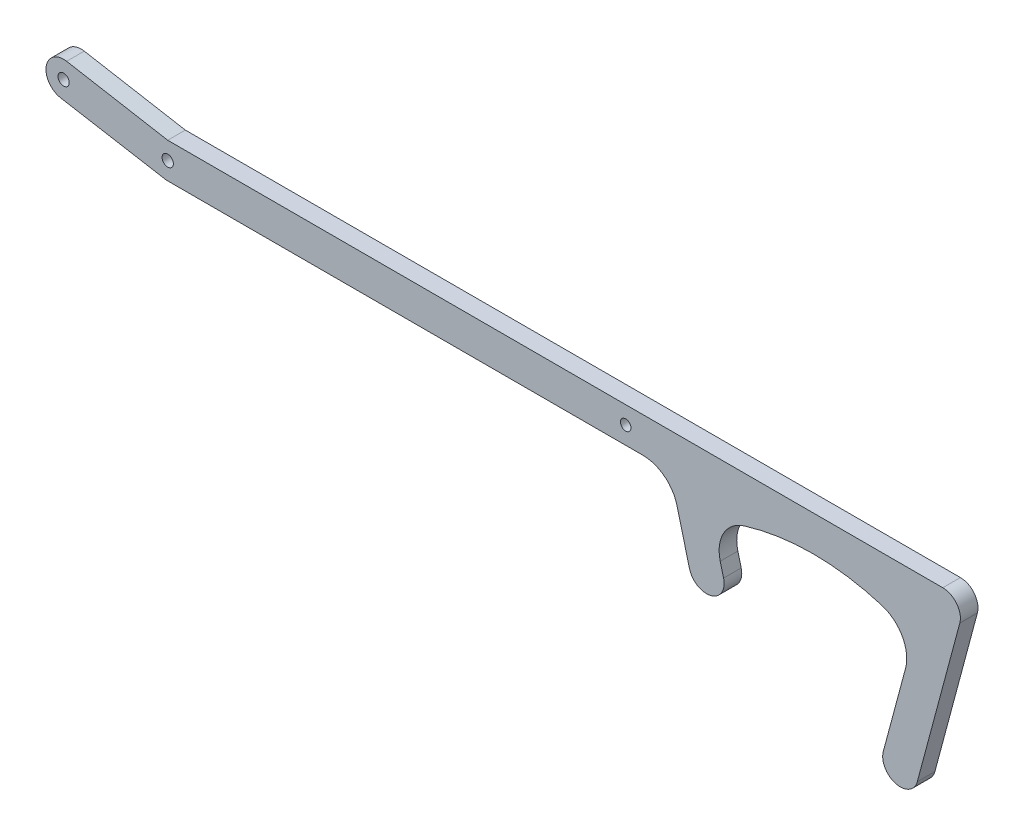
SolidWorks part; units mm, degrees
ref_plane "Front Plane" through (0, 0, 0) normal (0, 0, 1) x (1, 0, 0)
ref_plane "Top Plane" through (0, 0, 0) normal (0, 1, 0) x (1, 0, 0)
ref_plane "Right Plane" through (0, 0, 0) normal (1, 0, 0) x (0, 0, -1)
sketch "Sketch1" plane through (0, 0, 0) normal (0, 0, 1) x (1, 0, 0)
  line L0 (0, 0) -> (279.4, 0) construction
  line L1 (0, 6.35) -> (279.4, 6.35)
  line L2 (0, -6.35) -> (181.1202, -6.35)
  line L3 (285.5336, -1.6435) -> (270.2203, -58.7935)
  line L4 (257.9531, -55.5065) -> (268.9126, -14.605)
  line L6 (188.0883, -33.3375) -> (181.1202, -6.35)
  line L7 (200.3851, -30.1625) -> (196.3681, -14.605)
  line L8 (0, 0) -> (-37.5378, 6.521) construction
  line L10 (0, 6.35) -> (-36.4351, 12.7745)
  line L11 (-38.6246, 0.2647) -> (-1.0868, -6.2563)
  circle A0 centre (0, 0) radius 2.032
  arc A2 (285.5336, -1.6435) -> (279.4, 6.35) centre (279.4, 0) ccw
  arc A3 (257.9531, -55.5065) -> (270.2203, -58.7935) centre (264.0867, -57.15) ccw
  arc A5 (188.0883, -33.3375) -> (200.3851, -30.1625) centre (194.2367, -31.75) ccw
  arc A6 (196.3681, -14.605) -> (268.9126, -14.605) centre (232.6404, -90.8741) cw
  circle A7 centre (165.1, 0) radius 1.905
  arc A9 (-36.4351, 12.7745) -> (-38.6246, 0.2647) centre (-37.5378, 6.521) ccw
  circle A10 centre (-37.5378, 6.521) radius 2.032
  arc A12 (0, -6.35) -> (-1.0868, -6.2563) centre (0, 0) cw
  dimension "D1" = 31.75
  dimension "D3" = 6.35
  dimension "D5" = 6.35
  dimension "D6" = 6.35
  dimension "D11" = 4.064
  dimension "D14" = 17.145
  dimension "D10" = 75
  dimension "D13" = 84.455
  dimension "D15" = 3.81
  dimension "D19" = 6.35
  dimension "D21" = 4.064
  dimension "D17" = 6.35
  dimension "D4" = 12.7
  dimension "D7" = 279.4
  dimension "D8" = 57.15
  dimension "D9" = 69.85
  dimension "D12" = 26.9875
  dimension "D16" = 165.1
  dimension "D18" = 38.1
  dimension "D20" = 170
extrude "Boss-Extrude1" add sketch "Sketch1" along normal mid plane 6.35
fillet "Fillet1" radius 12.7 1 edges at (181.1202, -6.35, 0)
fillet "Fillet2" radius 12.7 2 edges at (268.9126, -14.605, 0) (196.3681, -14.605, 0)
sketch "Sketch2" plane through (0, 0, 3.175) normal (0, 0, 1) x (1, 0, 0)
  line L1 (251.2418, -10.754) -> (214.5821, -11.1379)
  line L2 (203.7836, -30.3021) -> (222.446, -61.8584)
  line L3 (244.4418, -61.628) -> (262.4392, -29.6878)
  circle A0 centre (233.1557, -34.228) radius 23.2833 construction
  arc A1 (222.446, -61.8584) -> (244.4418, -61.628) centre (233.3774, -55.3935) ccw
  arc A2 (251.2418, -10.754) -> (262.4392, -29.6878) centre (251.3748, -23.4533) cw
  arc A3 (214.5821, -11.1379) -> (203.7836, -30.3021) centre (214.715, -23.8372) ccw
  point P11 (0, 0)
  dimension "D1" = 12.7
  dimension "D2" = 44.45
ref_axis "Axis1" through (233.1557, -34.228, 3.175) along (0, 0, 1)
